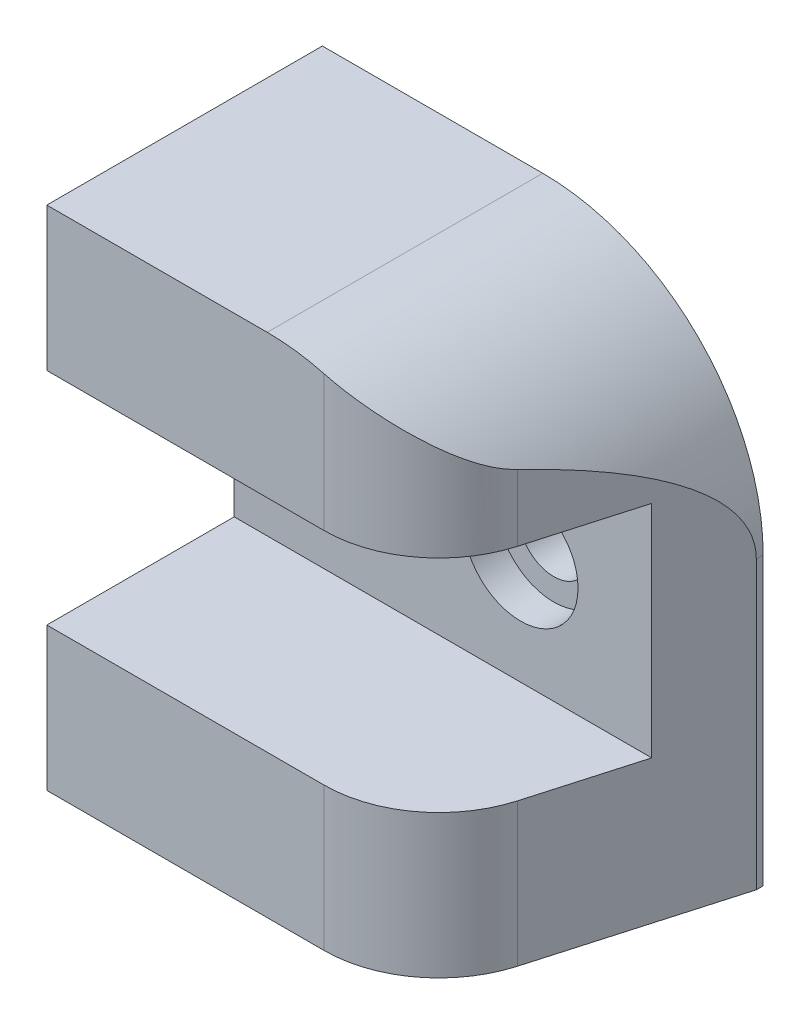
SolidWorks part; units mm, degrees
ref_plane "前视基准面" through (0, 0, 0) normal (0, 0, 1) x (1, 0, 0)
ref_plane "上视基准面" through (0, 0, 0) normal (0, 1, 0) x (1, 0, 0)
ref_plane "右视基准面" through (0, 0, 0) normal (1, 0, 0) x (0, 0, -1)
sketch "草图1" plane through (0, 0, 0) normal (0, 0, 1) x (1, 0, 0)
  line L0 (130, 95) -> (130, -95) construction
  line L1 (130, 82) -> (110, 82)
  line L2 (130, 82) -> (130, 95)
  line L3 (120, 105) -> (110, 105)
  line L4 (110, 82) -> (110, 105)
  line L5 (75, 105) -> (120, 105) construction
  line L6 (130, 105) -> (120, 105) construction
  line L7 (130, 95) -> (130, 105) construction
  arc A0 (130, 95) -> (120, 105) centre (120, 95) ccw construction
  arc A1 (130, 95) -> (120, 105) centre (120, 95) ccw
  dimension "D1" = 20
  dimension "D2" = 23
extrude "凸台-拉伸1" add sketch "草图1" along normal blind 12.5
sketch "草图2" plane through (0, 105, 0) normal (0, 1, 0) x (1, 0, 0)
  line L2 (127.5854, -8.732) -> (130.0065, -0.2886)
  line L4 (130.0065, -0.2886) -> (130.3236, -12.5)
  line L5 (130.3236, -12.5) -> (122.5851, -12.5)
  arc A1 (122.5851, -12.5) -> (127.5854, -8.732) centre (122.5851, -7.2982) ccw
extrude "切除-拉伸1" cut sketch "草图2" against normal blind 26.5
sketch "草图3" plane through (0, 0, 12.5) normal (0, 0, 1) x (1, 0, 0)
  line L0 (110, 93.5) -> (130, 93.5) construction
  line L1 (110, 105) -> (110, 82) construction
  line L2 (130, 95) -> (130, 82) construction
  line L4 (110, 98.5) -> (130, 98.5)
  line L5 (110, 98.5) -> (110, 88.5)
  line L6 (110, 88.5) -> (130, 88.5)
  line L7 (130, 98.5) -> (130, 88.5)
  line L8 (110, 98.5) -> (130, 88.5) construction
  line L9 (110, 88.5) -> (130, 98.5) construction
  point P6 (120, 93.5)
  dimension "D1" = 10
extrude "切除-拉伸2" cut sketch "草图3" against normal blind 8.5
sketch "草图4" plane through (0, 0, 4) normal (0, 0, 1) x (1, 0, 0)
  line L0 (110, 93.5) -> (128.9423, 93.5) construction
  line L1 (110, 98.5) -> (110, 88.5) construction
  line L2 (128.9423, 88.5) -> (128.9423, 98.5) construction
  circle A0 centre (115, 93.5) radius 1.5
  circle A2 centre (123, 93.5) radius 1.5
  dimension "D1" = 3
  dimension "D2" = 8
  dimension "D3" = 5
hole_wizard "M3 六角头螺栓的柱形沉头孔1" positions "草图7" profile "草图8" counterbore size "M3" standard "GB" end condition through all
sketch "草图7" plane through (0, 0, 4) normal (0, 0, 1) x (1, 0, 0)
  point P0 (115, 93.5)
  point P3 (123, 93.5)
sketch "草图8" plane through (115, 93.5, 4) normal (1, 0, 0) x (0, -1, 0)
  line L0 (0, 0) -> (0, 4)
  line L1 (0, 4) -> (1.6, 4)
  line L3 (1.6, 4) -> (1.6, 1.5)
  line L4 (1.6, 1.5) -> (2.6, 1.5)
  line L5 (2.6, 1.5) -> (2.6, 0)
  line L7 (2.6, 0) -> (0, 0)
  line L11 (0, -6.35) -> (0, 107.95) construction
  dimension "通孔孔直径" = 3.2
  dimension "通孔孔深度" = 4
  dimension "柱形沉头孔直径" = 5.2
  dimension "柱形沉头孔深度" = 1.5
move or copy body "实体-移动/复制1" [suppressed] bodies to move or copy 109
